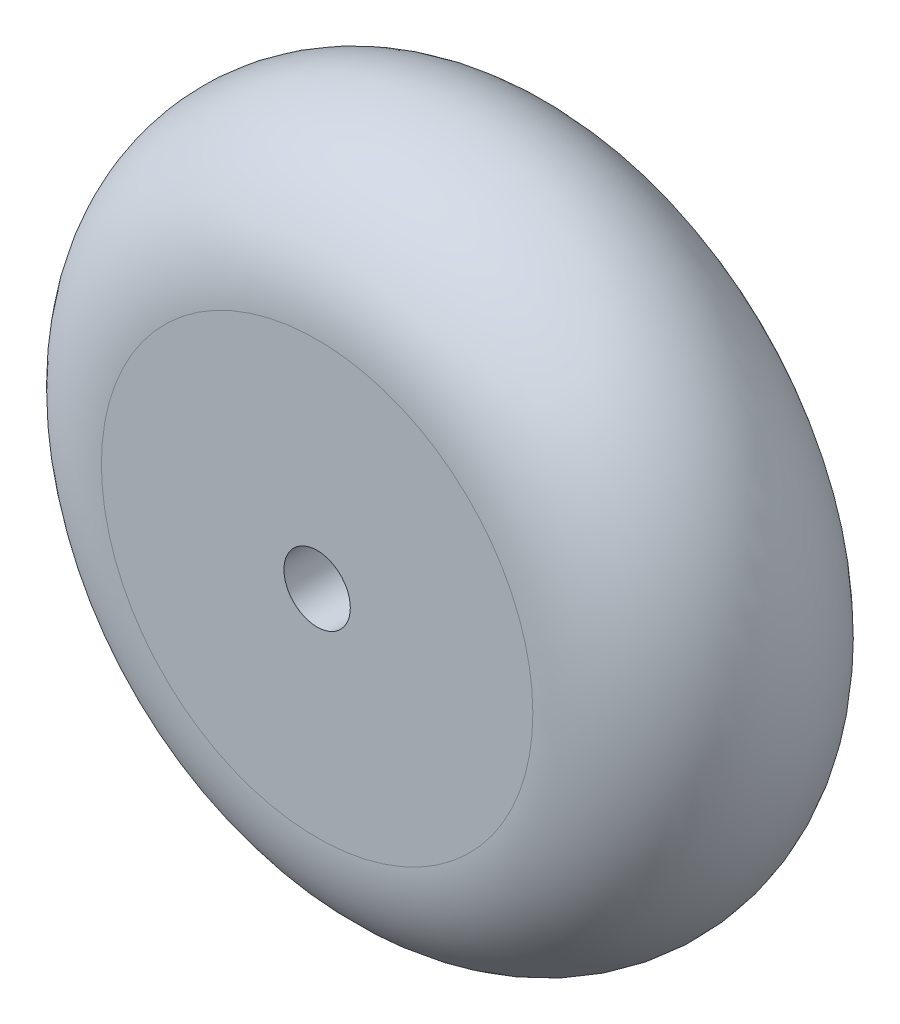
SolidWorks part; units mm, degrees
ref_plane "前视基准面" through (0, 0, 0) normal (0, 0, 1) x (1, 0, 0)
ref_plane "上视基准面" through (0, 0, 0) normal (0, 1, 0) x (1, 0, 0)
ref_plane "右视基准面" through (0, 0, 0) normal (1, 0, 0) x (0, 0, -1)
other "Configuration Table"
sketch "草图2" plane through (0, 0, 0) normal (0, 0, 1) x (1, 0, 0)
  circle A0 centre (0, 0) radius 19.5
  point P4 (0, 0)
  dimension "D1" = 39
extrude "凸台-拉伸1" add sketch "草图2" along normal blind 24
sketch "草图4" plane through (0, 0, 0) normal (1, 0, 0) x (0, 0, -1)
  line L0 (0, 19.5) -> (-24, 19.5) construction
  line L1 (-24, 19.5) -> (0, 19.5)
  line L2 (-38.2737, 0) -> (14.2737, 0) construction
  arc A0 (0, 19.5) -> (-24, 19.5) centre (-12, 19.5) ccw
  point P9 (-12, 0)
  dimension "D1" = 24
revolve "旋转1" add sketch "草图4" angle 360 about L2
sketch "草图5" plane through (0, 0, 24) normal (0, 0, 1) x (1, 0, 0)
  circle A0 centre (0, 0) radius 3
  dimension "D1" = 6
extrude "切除-拉伸1" cut sketch "草图5" against normal through all and the other way through all
ref_axis "基准轴1" through (0, 0, -57.2547) along (0, 0, 1)
ref_plane "基准面1" through (0, 0, 12) normal (0, 0, 1) x (1, 0, 0)
